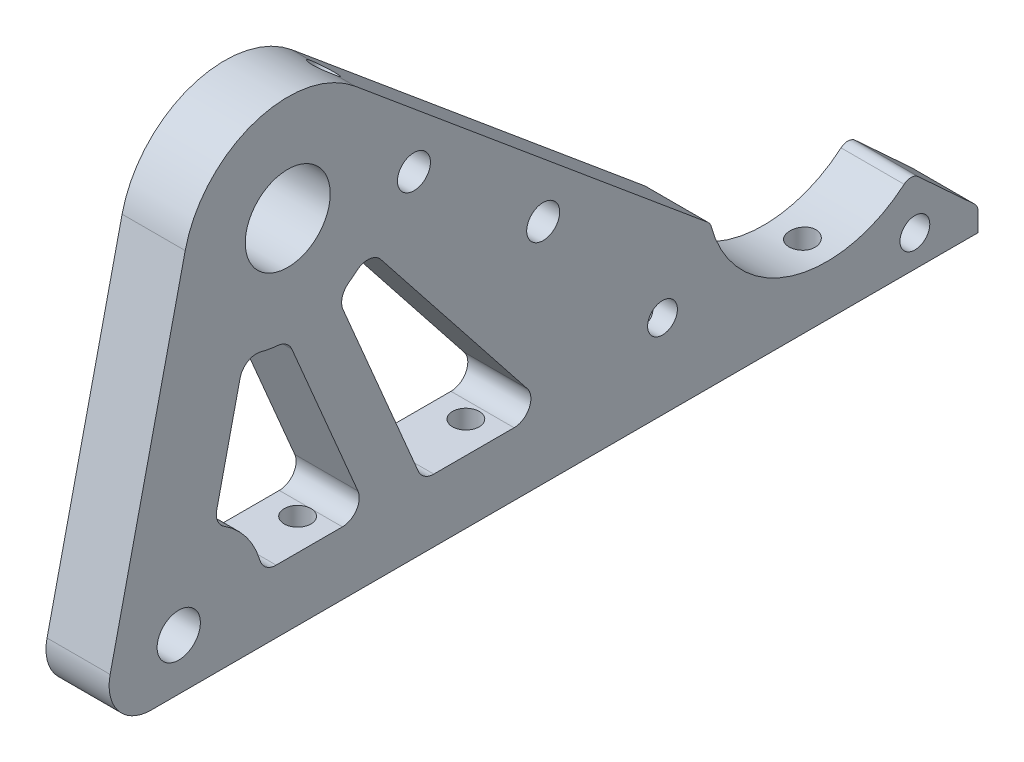
SolidWorks part; units mm, degrees
material "Alum Plate"
ref_plane "Front Plane" through (0, 0, 0) normal (0, 0, 1) x (1, 0, 0)
ref_plane "Top Plane" through (0, 0, 0) normal (0, 1, 0) x (1, 0, 0)
ref_plane "Right Plane" through (0, 0, 0) normal (1, 0, 0) x (0, 0, -1)
other "Bounding Box"
ref_plane "Default Plane" through (0, 2.286, 19.05) normal (0, -1, 0) x (-1, 0, 0)
sketch "Sketch1" plane through (0, 0, 0) normal (1, 0, 0) x (0, 0, -1)
  line L0 (-15.875, 0) -> (-15.875, -53.975)
  line L1 (-15.875, -53.975) -> (44.45, -53.975)
  line L2 (44.45, -53.975) -> (44.45, -16.4018)
  line L3 (10.1681, 12.1912) -> (44.45, -16.4018)
  circle A0 centre (0, 0) radius 6.4135
  arc A2 (10.1681, 12.1912) -> (-15.875, 0) centre (0, 0) ccw
  dimension "D1" = 12.827
  dimension "D2" = 31.75
  dimension "D3" = 53.975
  dimension "D4" = 60.325
  dimension "D5" = 50.17
extrude "Boss-Extrude1" add sketch "Sketch1" along normal blind 9.525
sketch "Sketch2" plane through (9.525, 0, 0) normal (1, 0, 0) x (0, 0, -1)
  line L1 (9.5885, -5.5359) -> (9.5885, 5.5359)
  line L2 (9.5885, 5.5359) -> (0, 11.0718)
  line L3 (0, 11.0718) -> (-9.5885, 5.5359)
  line L4 (-9.5885, 5.5359) -> (-9.5885, -5.5359)
  line L5 (-9.5885, -5.5359) -> (0, -11.0718)
  line L6 (0, -11.0718) -> (9.5885, -5.5359)
  circle A0 centre (0, 0) radius 9.5885 construction
  dimension "D1" = 19.177
extrude "Cut-Extrude1" [suppressed] cut sketch "Sketch2" against normal blind 3.175
sketch "Sketch3" [suppressed] plane through (9.525, 0, 0) normal (1, 0, 0) x (0, 0, -1)
  circle A0 centre (0, 8.9128) radius 2.25
  dimension "D1" = 4.5
  dimension "D2" = 2.159
extrude "Cut-Extrude2" [suppressed] cut sketch "Sketch3" against normal up to surface (3.175 mm away) up to face at (9.525, -20.7757, -12.6882)
pattern_circular "CirPattern1" [suppressed] count 6 over 360 reverse direction yes of bodies 167
fillet "Fillet1" [suppressed] radius 1.5875
sketch "Sketch4" plane through (9.525, 0, 0) normal (1, 0, 0) x (0, 0, -1)
  line L0 (19.05, -3.4214) -> (38.5559, -19.6904) construction
  line L1 (44.45, -16.4018) -> (10.1681, 12.1912) construction
  line L2 (0, 0) -> (19.05, -3.4214) construction
  circle A0 centre (19.05, -3.4214) radius 2.4892
  circle A1 centre (38.5559, -19.6904) radius 2.4892
  dimension "D1" = 25.4
  dimension "D3" = 4.9784
  dimension "D2" = 19.3548
  dimension "D4" = 19.05
extrude "Cut-Extrude3" cut sketch "Sketch4" against normal through all
sketch "Sketch5" plane through (9.525, 0, 0) normal (1, 0, 0) x (0, 0, -1)
  line L0 (0, 0) -> (81.3554, -28.2829) construction
  line L1 (44.45, -53.975) -> (44.45, -16.4018) construction
  line L2 (44.45, -53.975) -> (44.45, -16.4018)
  line L3 (-15.875, -53.975) -> (44.45, -53.975) construction
  line L4 (44.45, -16.4018) -> (64.0247, -23.1596)
  line L5 (104.19, -37.026) -> (104.19, -28.2829)
  line L6 (44.45, -53.975) -> (104.19, -53.975)
  line L7 (64.0247, -23.1596) -> (98.1556, -34.9428) construction
  line L8 (98.1556, -34.9428) -> (104.19, -37.026) construction
  line L9 (104.19, -37.026) -> (104.19, -53.975)
  line L10 (48.2368, -22.7475) -> (57.2883, -25.8724)
  line L11 (48.2368, -22.7475) -> (46.1646, -28.7498)
  line L12 (57.2883, -25.8724) -> (55.2161, -31.8747)
  line L13 (46.1646, -28.7498) -> (55.2161, -31.8747)
  line L15 (95.0928, -38.9237) -> (104.1444, -42.0486) construction
  line L16 (95.0928, -38.9237) -> (93.0206, -44.9261) construction
  line L17 (104.1444, -42.0486) -> (102.0722, -48.051) construction
  line L18 (93.0206, -44.9261) -> (102.0722, -48.051) construction
  line L19 (99.6186, -40.4862) -> (101.1728, -35.9844) construction
  line L20 (64.8516, -20.919) -> (47.9135, -13.3612)
  line L21 (47.9135, -13.3612) -> (49.8541, -9.012)
  line L22 (49.8541, -9.012) -> (62.9016, -14.8338)
  arc A0 (64.0247, -23.1596) -> (98.1556, -34.9428) centre (81.3554, -28.2829) ccw
  circle A1 centre (0, 0) radius 59.055 construction
  arc A2 (98.1556, -34.9428) -> (64.8516, -20.919) centre (81.3554, -28.2829) ccw
  arc A3 (64.2854, -22.3486) -> (64.0247, -23.1596) centre (81.3554, -28.2829) ccw construction
  circle A4 centre (56.565, -41.275) radius 2.2479
  circle A5 centre (94.665, -49.2125) radius 2.2479
  arc A6 (104.19, -28.2829) -> (62.9016, -14.8338) centre (81.3554, -28.2829) ccw
  arc A7 (102.5829, -36.6978) -> (59.787, -20.7847) centre (81.3554, -28.2829) ccw construction
  arc A8 (59.5193, -21.6042) -> (59.787, -20.7847) centre (81.3554, -28.2829) ccw construction
  arc A9 (60.5024, -18.9784) -> (59.5193, -21.6042) centre (81.3554, -28.2829) ccw construction
  arc A10 (62.9016, -14.8338) -> (60.5024, -18.9784) centre (81.3554, -28.2829) ccw construction
  arc A11 (64.8516, -20.919) -> (64.2854, -22.3486) centre (81.3554, -28.2829) ccw construction
  arc A12 (98.1556, -34.9428) -> (64.2854, -22.3486) centre (81.3554, -28.2829) ccw construction
  point P46 (52.7626, -24.3099)
  dimension "D1" = 118.11
  dimension "D3" = 36.1442
  dimension "D10" = 4.4958
  dimension "D2" = 86.1314
  dimension "D4" = 7.62
  dimension "D5" = 0.8128
  dimension "D6" = 9.5758
  dimension "D7" = 6.35
  dimension "D8" = 4.7625
  dimension "D9" = 5
  dimension "D11" = 4.7625
  dimension "D12" = 9.525
  dimension "D13" = 12.7
  dimension "D15" = 4.7625
  dimension "D16" = 14.2875
  dimension "D17" = 47.625
  dimension "D18" = 8.3126
  dimension "D14" = 4.7625
extrude "Boss-Extrude2" add sketch "Sketch5" against normal up to surface (9.525 mm away) up to face at (0, -3.4214, -21.5392)
fillet "Fillet3" radius 1.5875 6 edges at (4.7625, -14.8338, -62.9016) (4.7625, -16.4018, -44.45) (4.7625, -9.012, -49.8541) (4.7625, -13.3612, -47.9135) (4.7625, -23.1596, -64.0247) (4.7625, -20.919, -64.8516)
sketch "Sketch6" plane through (9.525, 0, 0) normal (1, 0, 0) x (0, 0, -1)
  line L0 (56.7188, -12.075) -> (56.8678, -12.4186)
  line L1 (62.6458, -22.6836) -> (44.7252, -16.4968) construction
  line L2 (56.8678, -12.4186) -> (57.1827, -12.282)
  line L3 (57.1827, -12.282) -> (56.7188, -12.075)
  line L4 (56.9507, -12.1785) -> (56.8678, -12.4186) construction
  line L5 (56.8678, -12.4186) -> (52.7626, -24.3099) construction
  line L6 (57.2883, -25.8724) -> (48.2368, -22.7475) construction
  line L14 (61.7604, -14.3246) -> (51.3038, -9.6588) construction
  line L15 (52.6015, -10.2379) -> (61.2999, -14.1191) construction
  point P12 (56.9507, -12.1785)
  dimension "D1" = 0.508
  dimension "D2" = 0.254
  dimension "D3" = 9.525
extrude "Cut-Extrude4" cut sketch "Sketch6" against normal through all
sketch "Sketch7" plane through (9.525, 0, 0) normal (1, 0, 0) x (0, 0, -1)
  line L0 (46.1646, -28.7498) -> (55.2161, -31.8747) construction
  line L1 (55.2161, -31.8747) -> (57.2883, -25.8724) construction
  line L2 (57.2883, -25.8724) -> (48.2368, -22.7475) construction
  line L3 (48.2368, -22.7475) -> (46.1646, -28.7498) construction
  line L4 (46.1646, -28.7498) -> (55.2161, -31.8747)
  line L5 (55.2161, -31.8747) -> (57.2883, -25.8724)
  line L6 (57.2883, -25.8724) -> (48.2368, -22.7475)
  line L7 (48.2368, -22.7475) -> (46.1646, -28.7498)
extrude "Boss-Extrude3" add sketch "Sketch7" against normal up to surface (9.525 mm away) up to face at (0, -3.4214, -21.5392)
sketch "Sketch8" plane through (9.525, 0, 0) normal (1, 0, 0) x (0, 0, -1)
  line L0 (42.4919, -8.0437) -> (44.2264, -16.2154)
  line L3 (94.0735, -41.1223) -> (104.19, -50.4444)
  line L4 (104.19, -53.975) -> (104.19, -28.2829) construction
  line L5 (104.19, -50.4444) -> (124.1478, -21.1253)
  line L6 (124.1478, -21.1253) -> (84.3854, 15.515)
  line L7 (84.3854, 15.515) -> (42.4919, -8.0437)
  line L8 (-15.875, -53.975) -> (104.19, -53.975) construction
  line L10 (44.2264, -16.2154) -> (63.79, -32.5325)
  line L12 (44.2264, -16.2154) -> (10.1681, 12.1912) construction
  arc A0 (63.6804, -24.5152) -> (65.5002, -19.6103) centre (81.3554, -28.2829) ccw construction
  arc A4 (63.79, -32.5325) -> (94.0735, -41.1223) centre (81.3554, -28.2829) ccw
  dimension "D2" = 3.5306
  dimension "D3" = 42.66
extrude "Cut-Extrude5" cut sketch "Sketch8" against normal through all
fillet "Fillet4" radius 1.5875 3 edges at (4.7625, -41.1223, -94.0735) (4.7625, -50.4444, -104.19) (4.7625, -32.5325, -63.79)
sketch "Sketch9" plane through (9.525, 0, 0) normal (1, 0, 0) x (0, 0, -1)
  line L0 (-15.4786, 3.5254) -> (-28.575, -53.975)
  line L1 (-28.575, -53.975) -> (-15.875, -53.975)
  line L2 (-15.875, 0) -> (-15.875, -53.975) construction
  line L3 (-15.875, 0) -> (-15.875, -53.975)
  line L4 (-15.875, -53.975) -> (104.19, -53.975) construction
  arc A0 (10.1681, 12.1912) -> (-15.875, 0) centre (0, 0) ccw construction
  arc A1 (-15.4786, 3.5254) -> (-15.875, 0) centre (0, 0) ccw
  dimension "D1" = 12.7
extrude "Boss-Extrude4" add sketch "Sketch9" against normal up to surface (9.525 mm away) up to face at (0, -3.4214, -21.5392)
sketch "Sketch10" plane through (9.525, 0, 0) normal (1, 0, 0) x (0, 0, -1)
  line L0 (-28.575, -53.975) -> (104.19, -53.975) construction
  circle A1 centre (-16.4523, -46.2527) radius 3.2639
  dimension "D3" = 6.5278
  dimension "D1" = 46.2527
  dimension "D2" = 16.4523
  dimension "D4" = 7.7223
extrude "Cut-Extrude6" cut sketch "Sketch10" against normal through all
fillet "Fillet5" radius 6.35 1 edges at (4.7625, -53.975, 28.575)
sketch "Sketch13" plane through (9.525, 0, 0) normal (1, 0, 0) x (0, 0, -1)
  line L0 (-6.5643, -14.524) -> (-11.1412, -34.6188)
  line L1 (-15.4786, 3.5254) -> (-26.8075, -46.2148) construction
  line L2 (0, -15.9385) -> (12.0839, -44.45)
  line L3 (12.0839, -44.45) -> (-3.7911, -44.45)
  line L4 (7.4849, -14.0717) -> (20.3601, -44.45)
  line L5 (20.3601, -44.45) -> (39.4101, -44.45)
  line L6 (39.4101, -44.45) -> (12.2805, -10.16)
  line L7 (-20.6161, -53.975) -> (104.19, -53.975) construction
  arc A0 (0, -15.9385) -> (7.4849, -14.0717) centre (0, 0) ccw construction
  arc A1 (7.4849, -14.0717) -> (12.2805, -10.16) centre (0, 0) ccw
  circle A2 centre (0, 0) radius 15.9385
  arc A3 (-6.5643, -14.524) -> (0, -15.9385) centre (0, 0) ccw
  circle A5 centre (-16.4523, -46.2527) radius 12.7889
  arc A6 (-3.7911, -44.45) -> (-11.1412, -34.6188) centre (-16.4523, -46.2527) ccw
  dimension "D3" = 12.7
  dimension "D4" = 9.525
  dimension "D5" = 15.875
  dimension "D6" = 7.62
  dimension "D7" = 19.05
  dimension "D8" = 10.16
  dimension "D1" = 9.525
  dimension "D2" = 9.525
extrude "Cut-Extrude9" cut sketch "Sketch13" against normal through all
fillet "Fillet6" radius 2.54 9 edges at (4.7625, -44.45, -39.4101) (4.7625, -44.45, -20.3601) (4.7625, -14.0717, -7.4849) (4.7625, -10.16, -12.2805) (4.7625, -44.45, -12.0839) (4.7625, -44.45, 3.7911) (4.7625, -34.6188, 11.1412) (4.7625, -15.9385, 0) (4.7625, -14.524, 6.5643)
sketch "Sketch14" plane through (0, 12.1912, -10.1681) normal (0, 0.7679, -0.6405) x (1, 0, 0)
  line L2 (9.525, 0) -> (0, 0) construction
  circle A0 centre (4.7625, 0) radius 2.0193
  dimension "D1" = 4.0386
extrude "Cut-Extrude10" cut sketch "Sketch14" against normal up to next
sketch "Sketch16" plane through (0, -53.975, 0) normal (0, -1, 0) x (1, 0, 0)
  line L0 (4.7625, -6.2489) -> (4.7625, 20.6161) construction
  line L1 (9.525, 20.6161) -> (0, 20.6161) construction
  line L2 (9.525, -6.4135) -> (9.525, 6.4135) construction
  line L3 (9.525, -6.4135) -> (9.525, 6.4135) construction
  circle A0 centre (4.7625, -6.2489) radius 2.0193
  point P8 (9.525, 0)
  dimension "D1" = 4.0386
  dimension "D2" = 6.2489
extrude "Cut-Extrude11" cut sketch "Sketch16" against normal blind 12.7
pattern_linear "LPattern2" count 4 spacing 25.4 along (0, 0, -1) of "Cut-Extrude11"
equation "\"Unit Measure\"= \"BoundingVolume\" / \"Thickness\"'in^2"
